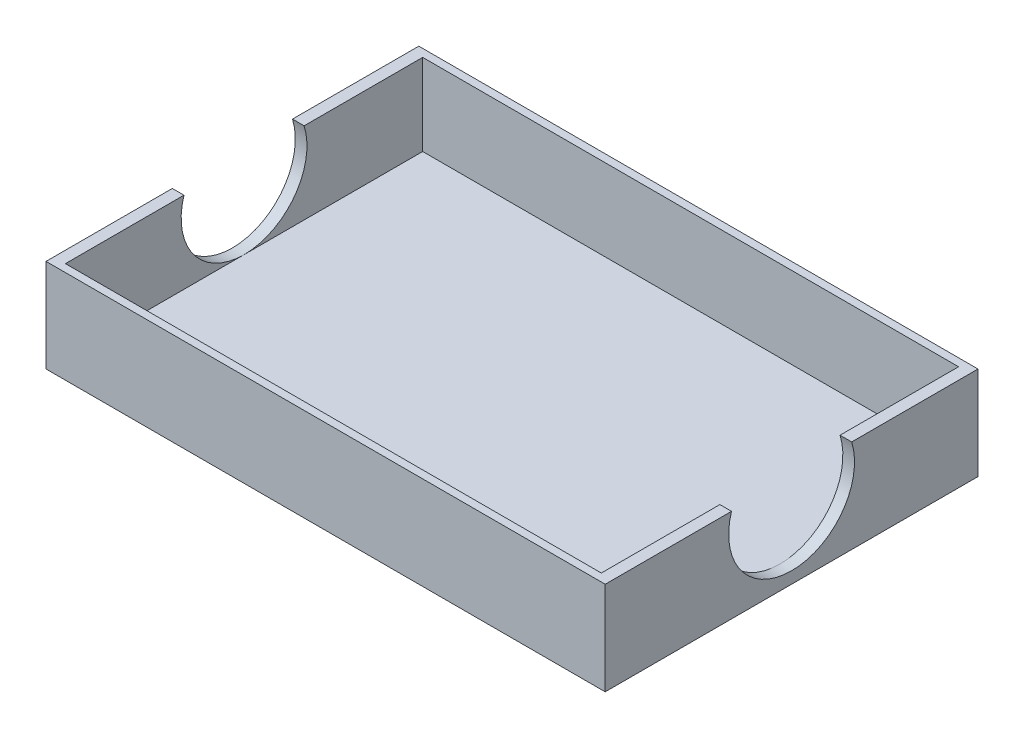
SolidWorks part; units mm, degrees
ref_plane "Front Plane" through (0, 0, 0) normal (0, 0, 1) x (1, 0, 0)
ref_plane "Top Plane" through (0, 0, 0) normal (0, 1, 0) x (1, 0, 0)
ref_plane "Right Plane" through (0, 0, 0) normal (1, 0, 0) x (0, 0, -1)
sketch "Sketch1" plane through (0, 0, 0) normal (0, 1, 0) x (1, 0, 0)
  line L1 (-60, -40) -> (60, -40)
  line L2 (-60, -40) -> (-60, 40)
  line L3 (-60, 40) -> (60, 40)
  line L4 (60, -40) -> (60, 40)
  line L5 (-60, -40) -> (60, 40) construction
  line L6 (-60, 40) -> (60, -40) construction
  line L11 (57.5, 38.3333) -> (-57.5, 38.3333)
  line L12 (57.5, 38.3333) -> (57.5, -38.3333)
  line L13 (57.5, -38.3333) -> (-57.5, -38.3333)
  line L14 (-57.5, 38.3333) -> (-57.5, -38.3333)
  line L15 (57.5, 38.3333) -> (-57.5, -38.3333) construction
  line L16 (57.5, -38.3333) -> (-57.5, 38.3333) construction
  point P0 (0, 0)
  point P6 (0, 0)
  dimension "D1" = 120
  dimension "D2" = 80
  dimension "D3" = 2.5
extrude "Boss-Extrude1" add sketch "Sketch1" along normal blind 20
extrude "Boss-Extrude2" add sketch "Sketch1<3>" along normal blind 2.5 contours L11 L14 L13 L12 region at (0, 0, 0)
sketch "Sketch1<3>" plane through (0, 0, 0) normal (0, 1, 0) x (1, 0, 0) same geometry as "Sketch1"
sketch "Sketch2" plane through (-60, 0, 0) normal (-1, 0, 0) x (0, 0, 1)
  line L1 (-40, 0) -> (40, 0) construction
  circle A0 centre (0, 16) radius 13.5
  dimension "D1" = 27
  dimension "D2" = 2.5
extrude "Cut-Extrude1" cut sketch "Sketch2" against normal through all
